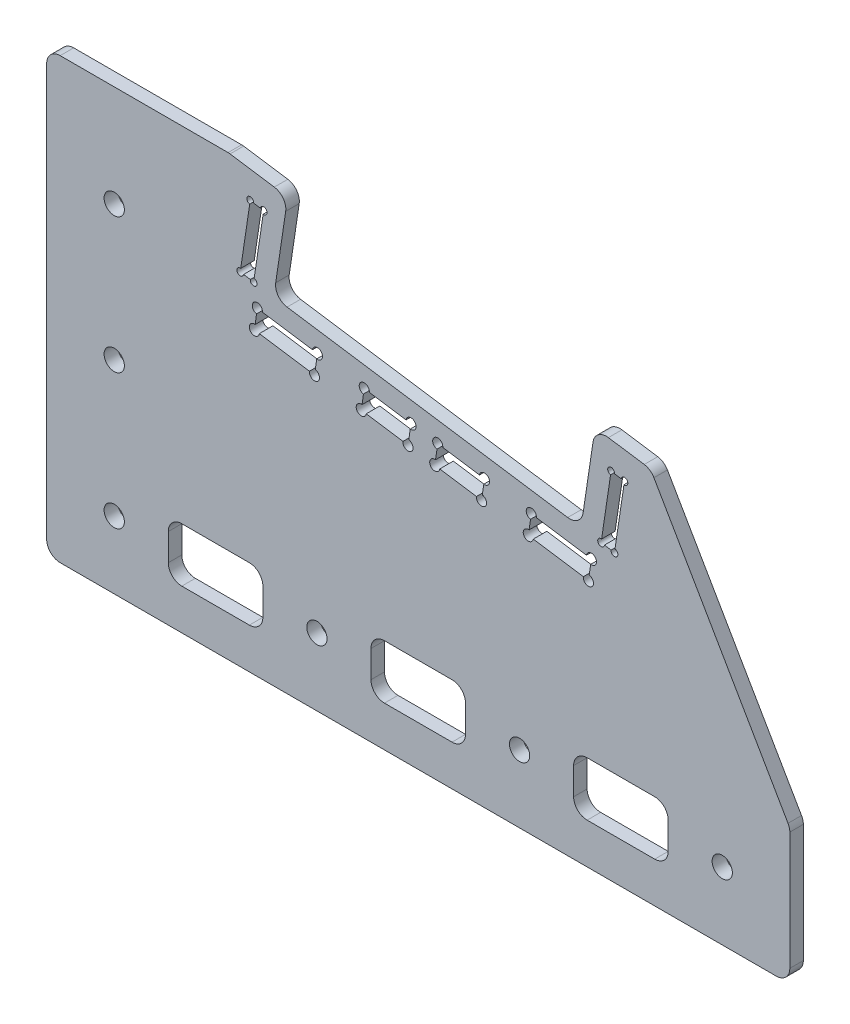
SolidWorks part; units mm, degrees
material "Thornel Mat VMA"
ref_plane "前视基准面" through (0, 0, 0) normal (0, 0, 1) x (1, 0, 0)
ref_plane "上视基准面" through (0, 0, 0) normal (0, 1, 0) x (1, 0, 0)
ref_plane "右视基准面" through (0, 0, 0) normal (1, 0, 0) x (0, 0, -1)
sketch "草图1" plane through (0, 0, 0) normal (0, 0, 1) x (1, 0, 0)
  line L1 (0, 0) -> (110, 0)
  line L2 (0, 0) -> (0, 65)
  line L3 (0, 65) -> (110, 65)
  line L4 (110, 0) -> (110, 65)
  circle A0 centre (10, 10) radius 1.5
  circle A1 centre (10, 30) radius 1.5
  circle A2 centre (10, 50) radius 1.5
  circle A3 centre (40, 10) radius 1.5
  circle A4 centre (70, 10) radius 1.5
  circle A5 centre (100, 10) radius 1.5
  dimension "D3" = 3
  dimension "D1" = 65
  dimension "D2" = 110
  dimension "D4" = 10
  dimension "D5" = 10
  dimension "D6" = 20
  dimension "D7" = 20
  dimension "D8" = 30
  dimension "D9" = 30
  dimension "D10" = 30
extrude "凸台-拉伸1" add sketch "草图1" along normal blind 2
sketch "草图2" plane through (0, 0, 2) normal (0, 0, 1) x (1, 0, 0)
  line L0 (27, 65) -> (110, 52.5956)
  line L1 (110, 65) -> (0, 65) construction
  line L2 (110, 0) -> (110, 65) construction
  line L3 (0, 65) -> (0, 0) construction
  line L4 (27, 65) -> (110, 65)
  line L5 (110, 65) -> (110, 52.5956)
  dimension "D1" = 27
  dimension "D2" = 8.5
extrude "切除-拉伸1" cut sketch "草图2" against normal through all
sketch "草图3" plane through (0, 0, 2) normal (0, 0, 1) x (1, 0, 0)
  line L0 (35.6737, 63.7037) -> (81.1684, 56.9045)
  line L1 (35.6737, 63.7037) -> (33.6043, 49.8575)
  line L2 (81.1684, 56.9045) -> (79.0991, 43.0583)
  line L3 (33.6043, 49.8575) -> (79.0991, 43.0583)
  line L4 (27, 65) -> (110, 52.5956) construction
  dimension "D1" = 14
  dimension "D2" = 46
  dimension "D3" = 8.77
extrude "切除-拉伸2" cut sketch "草图3" against normal through all
sketch "草图4" plane through (0, 0, 2) normal (0, 0, 1) x (1, 0, 0)
  line L0 (30.1939, 47.3339) -> (81.6227, 39.6478) construction
  line L1 (33.6043, 49.8575) -> (79.0991, 43.0583) construction
  line L2 (35.6737, 63.7037) -> (33.6043, 49.8575) construction
  line L3 (79.0991, 43.0583) -> (81.1684, 56.9045) construction
  line L4 (30.1939, 47.3339) -> (32.7066, 64.1471) construction
  line L5 (27, 65) -> (35.6737, 63.7037) construction
  line L6 (81.6227, 39.6478) -> (84.1354, 56.4611) construction
  line L7 (81.1684, 56.9045) -> (110, 52.5956) construction
  line L8 (32.1154, 60.1911) -> (30.6373, 50.3009)
  line L9 (32.1154, 60.1911) -> (30.1275, 60.4882)
  line L10 (30.6373, 50.3009) -> (28.6494, 50.598)
  line L11 (30.1275, 60.4882) -> (28.6494, 50.598)
  line L12 (83.5442, 52.505) -> (82.0661, 42.6148)
  line L13 (83.5442, 52.505) -> (85.5222, 52.2094)
  line L14 (82.0661, 42.6148) -> (84.0441, 42.3192)
  line L15 (85.5222, 52.2094) -> (84.0441, 42.3192)
  line L16 (31.1829, 47.1861) -> (40.084, 45.8558)
  line L17 (31.1829, 47.1861) -> (30.7394, 44.219)
  line L18 (40.084, 45.8558) -> (39.6406, 42.8887)
  line L19 (30.7394, 44.219) -> (39.6406, 42.8887)
  line L20 (47.0071, 44.8211) -> (53.9302, 43.7864)
  line L21 (47.0071, 44.8211) -> (46.5637, 41.8541)
  line L22 (53.9302, 43.7864) -> (53.4868, 40.8194)
  line L23 (46.5637, 41.8541) -> (53.4868, 40.8194)
  line L24 (57.8863, 43.1952) -> (64.8094, 42.1605)
  line L25 (57.8863, 43.1952) -> (57.4429, 40.2282)
  line L26 (64.8094, 42.1605) -> (64.366, 39.1935)
  line L27 (57.4429, 40.2282) -> (64.366, 39.1935)
  line L28 (71.7325, 41.1259) -> (80.6337, 39.7956)
  line L29 (71.7325, 41.1259) -> (71.2891, 38.1588)
  line L30 (80.6337, 39.7956) -> (80.1902, 36.8285)
  line L31 (71.2891, 38.1588) -> (80.1902, 36.8285)
  point P21 (30.9612, 45.7025)
  point P37 (39.8623, 44.3723)
  dimension "D1" = 3
  dimension "D2" = 3
  dimension "D3" = 3
  dimension "D4" = 1
  dimension "D5" = 2
  dimension "D6" = 9
  dimension "D7" = 9
  dimension "D8" = 1.5
  dimension "D9" = 7
  dimension "D10" = 7
  dimension "D11" = 7
  dimension "D12" = 7
  dimension "D13" = 1
  dimension "D14" = 3
  dimension "D15" = 3
  dimension "D16" = 3
  dimension "D17" = 3
  dimension "D18" = 10
  dimension "D19" = 2.01
  dimension "D20" = 3
  dimension "D21" = 10
extrude "切除-拉伸3" cut sketch "草图4" against normal through all
sketch "草图5" plane through (0, 0, 2) normal (0, 0, 1) x (1, 0, 0)
  line L0 (93.3849, 51.0343) -> (91.9068, 41.1441)
  line L1 (93.3849, 51.0343) -> (96.352, 50.5909)
  line L2 (91.9068, 41.1441) -> (94.8739, 40.7007)
  line L3 (96.352, 50.5909) -> (94.8739, 40.7007)
  line L4 (82.0661, 42.6148) -> (84.0441, 42.3192) construction
  line L5 (84.0441, 42.3192) -> (85.5222, 52.2094) construction
  dimension "D1" = 7.95
  dimension "D2" = 3
  dimension "D3" = 10
extrude "切除-拉伸4" [suppressed] cut sketch "草图5" against normal through all
sketch "草图6" plane through (0, 0, 2) normal (0, 0, 1) x (1, 0, 0)
  circle A0 centre (30.7394, 44.219) radius 0.75
  circle A1 centre (31.1829, 47.1861) radius 0.75
  circle A2 centre (40.084, 45.8558) radius 0.75
  circle A3 centre (39.6406, 42.8887) radius 0.75
  circle A4 centre (53.4868, 40.8194) radius 0.75
  circle A5 centre (46.5637, 41.8541) radius 0.75
  circle A6 centre (47.0071, 44.8211) radius 0.75
  circle A7 centre (53.9302, 43.7864) radius 0.75
  circle A8 centre (57.8863, 43.1952) radius 0.75
  circle A9 centre (57.4429, 40.2282) radius 0.75
  circle A10 centre (64.366, 39.1935) radius 0.75
  circle A11 centre (64.8094, 42.1605) radius 0.75
  circle A12 centre (80.1902, 36.8285) radius 0.75
  circle A13 centre (80.6337, 39.7956) radius 0.75
  circle A14 centre (71.7325, 41.1259) radius 0.75
  circle A15 centre (71.2891, 38.1588) radius 0.75
  circle A16 centre (30.6373, 50.3009) radius 0.5
  circle A17 centre (28.6494, 50.598) radius 0.5
  circle A18 centre (30.1275, 60.4882) radius 0.5
  circle A19 centre (32.1154, 60.1911) radius 0.5
  circle A20 centre (84.0441, 42.3192) radius 0.5
  circle A21 centre (82.0661, 42.6148) radius 0.5
  circle A22 centre (83.5442, 52.505) radius 0.5
  circle A23 centre (85.5222, 52.2094) radius 0.5
  dimension "D1" = 1
  dimension "D2" = 1.5
extrude "切除-拉伸5" cut sketch "草图6" against normal blind 10
sketch "草图7" plane through (0, 0, 2) normal (0, 0, 1) x (1, 0, 0)
  line L0 (0, 20) -> (110, 20) construction
  line L1 (0, 65) -> (0, 0) construction
  line L2 (110, 0) -> (110, 52.5956) construction
  line L3 (0, 0) -> (110, 0) construction
  line L4 (110, 20) -> (89.4038, 55.6737)
  line L5 (81.1684, 56.9045) -> (110, 52.5956) construction
  line L6 (89.4038, 55.6737) -> (110, 52.5956)
  line L7 (110, 52.5956) -> (110, 20)
  dimension "D1" = 20
  dimension "D2" = 60
extrude "切除-拉伸6" cut sketch "草图7" against normal blind 10
fillet "圆角1" radius 2 10 edges at (110, 0, 1) (27, 65, 1) (35.6737, 63.7037, 1) (33.6043, 49.8575, 1) (79.0991, 43.0583, 1) (81.1684, 56.9045, 1) (89.4038, 55.6737, 1) (110, 20, 1) (0, 65, 1) (0, 0, 1)
sketch "草图8" plane through (0, 0, 0) normal (0, 0, -1) x (-1, 0, 0)
  line L0 (-90, 14) -> (-80, 14) construction
  line L1 (-92, 8) -> (-92, 12) construction
  line L2 (-80, 6) -> (-90, 6) construction
  line L3 (-78, 12) -> (-78, 8) construction
  line L4 (-62, 8) -> (-62, 12) construction
  line L5 (-50, 6) -> (-60, 6) construction
  line L6 (-60, 14) -> (-50, 14) construction
  line L7 (-48, 12) -> (-48, 8) construction
  line L8 (-30, 14) -> (-20, 14) construction
  line L9 (-32, 8) -> (-32, 12) construction
  line L10 (-20, 6) -> (-30, 6) construction
  line L11 (-18, 12) -> (-18, 8) construction
  line L12 (-90, 14) -> (-80, 14)
  line L13 (-92, 8) -> (-92, 12)
  line L14 (-80, 6) -> (-90, 6)
  line L15 (-78, 12) -> (-78, 8)
  line L16 (-62, 8) -> (-62, 12)
  line L17 (-50, 6) -> (-60, 6)
  line L18 (-60, 14) -> (-50, 14)
  line L19 (-48, 12) -> (-48, 8)
  line L20 (-30, 14) -> (-20, 14)
  line L21 (-32, 8) -> (-32, 12)
  line L22 (-20, 6) -> (-30, 6)
  line L23 (-18, 12) -> (-18, 8)
  arc A0 (-78, 12) -> (-80, 14) centre (-80, 12) ccw construction
  arc A1 (-90, 14) -> (-92, 12) centre (-90, 12) ccw construction
  arc A2 (-92, 8) -> (-90, 6) centre (-90, 8) ccw construction
  arc A3 (-80, 6) -> (-78, 8) centre (-80, 8) ccw construction
  arc A4 (-60, 14) -> (-62, 12) centre (-60, 12) ccw construction
  arc A5 (-62, 8) -> (-60, 6) centre (-60, 8) ccw construction
  arc A6 (-48, 12) -> (-50, 14) centre (-50, 12) ccw construction
  arc A7 (-50, 6) -> (-48, 8) centre (-50, 8) ccw construction
  arc A8 (-30, 14) -> (-32, 12) centre (-30, 12) ccw construction
  arc A9 (-32, 8) -> (-30, 6) centre (-30, 8) ccw construction
  arc A10 (-18, 12) -> (-20, 14) centre (-20, 12) ccw construction
  arc A11 (-20, 6) -> (-18, 8) centre (-20, 8) ccw construction
  arc A12 (-78, 12) -> (-80, 14) centre (-80, 12) ccw
  arc A13 (-90, 14) -> (-92, 12) centre (-90, 12) ccw
  arc A14 (-92, 8) -> (-90, 6) centre (-90, 8) ccw
  arc A15 (-80, 6) -> (-78, 8) centre (-80, 8) ccw
  arc A16 (-60, 14) -> (-62, 12) centre (-60, 12) ccw
  arc A17 (-62, 8) -> (-60, 6) centre (-60, 8) ccw
  arc A18 (-48, 12) -> (-50, 14) centre (-50, 12) ccw
  arc A19 (-50, 6) -> (-48, 8) centre (-50, 8) ccw
  arc A20 (-30, 14) -> (-32, 12) centre (-30, 12) ccw
  arc A21 (-32, 8) -> (-30, 6) centre (-30, 8) ccw
  arc A22 (-18, 12) -> (-20, 14) centre (-20, 12) ccw
  arc A23 (-20, 6) -> (-18, 8) centre (-20, 8) ccw
extrude "切除-拉伸7" cut sketch "草图8" against normal through all
